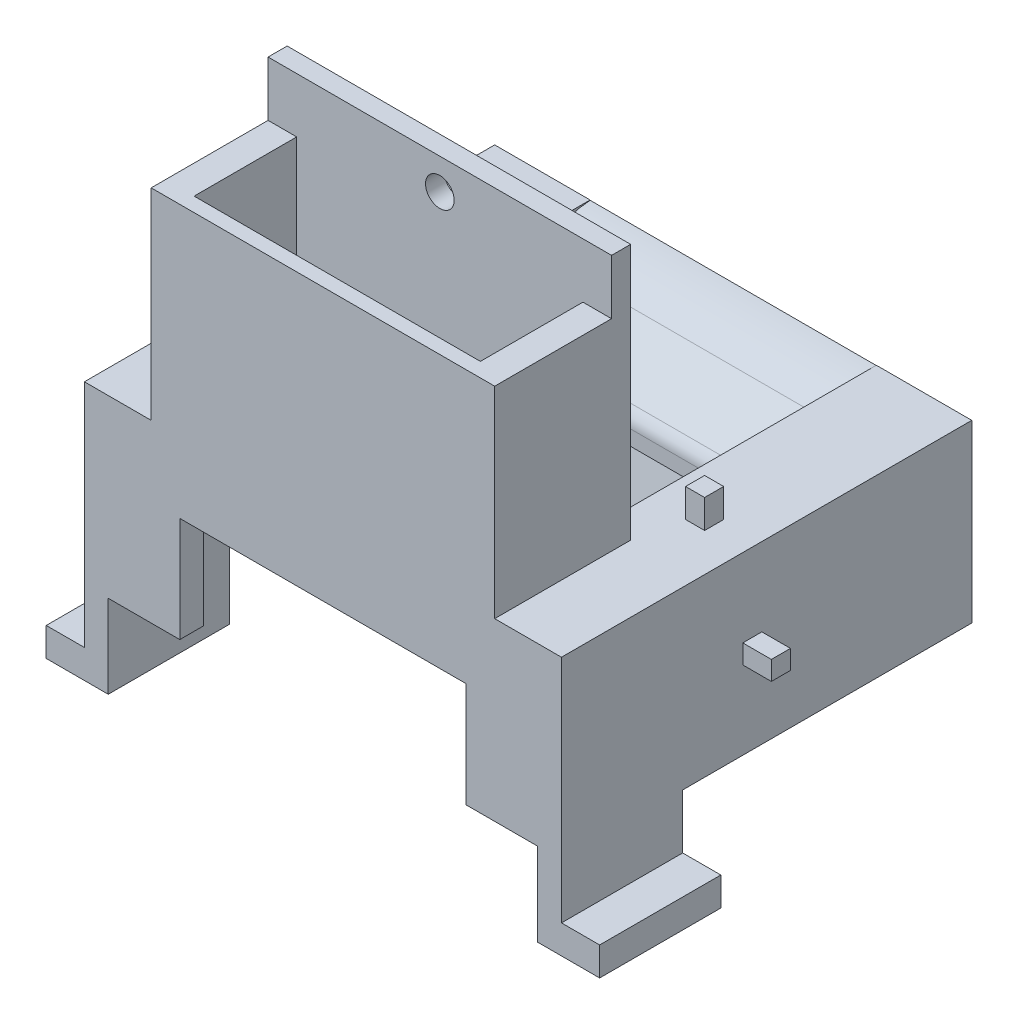
SolidWorks part; units mm, degrees
ref_plane "Front Plane" through (0, 0, 0) normal (0, 0, 1) x (1, 0, 0)
ref_plane "Top Plane" through (0, 0, 0) normal (0, 1, 0) x (1, 0, 0)
ref_plane "Right Plane" through (0, 0, 0) normal (1, 0, 0) x (0, 0, -1)
sketch "Sketch1" plane through (0, 0, 0) normal (0, 0, 1) x (1, 0, 0)
  line L1 (-25, 9.2) -> (25, 9.2)
  line L2 (-25, 9.2) -> (-25, -9.2)
  line L3 (-25, -9.2) -> (25, -9.2)
  line L4 (25, 9.2) -> (25, -9.2)
  line L5 (-25, 9.2) -> (25, -9.2) construction
  line L6 (-25, -9.2) -> (25, 9.2) construction
  point P0 (0, 0)
  dimension "D1" = 50
  dimension "D2" = 18.4
extrude "Boss-Extrude1" add sketch "Sketch1" along normal blind 43
sketch "Sketch2" plane through (0, -9.2, 0) normal (0, -1, 0) x (-1, 0, 0)
  line L0 (-25, -43) -> (-25, 0) construction
  line L1 (-22.5, -14.5) -> (-15, -14.5)
  line L2 (-22.5, -14.5) -> (-22.5, -9.5)
  line L3 (-22.5, -9.5) -> (-15, -9.5)
  line L4 (-15, -14.5) -> (-15, -9.5)
  line L5 (25, 0) -> (-25, 0) construction
  line L6 (22.5, -14.5) -> (15, -14.5)
  line L7 (22.5, -14.5) -> (22.5, -9.5)
  line L8 (22.5, -9.5) -> (15, -9.5)
  line L9 (15, -14.5) -> (15, -9.5)
  line L10 (-22.5, -12) -> (-25, -12) construction
  line L11 (15, -12.9) -> (-15, -12.9)
  line L12 (15, -12.9) -> (15, -11.1)
  line L13 (15, -11.1) -> (-15, -11.1)
  line L14 (-15, -12.9) -> (-15, -11.1)
  line L15 (22.5, -12) -> (25, -12) construction
  line L19 (25, -43) -> (25, 0) construction
  point P12 (15, -12)
  point P13 (-15, -12)
  point P15 (15, -12)
  line M14 (-25, 0) -> (-25, -43)
  line M16 (25, -43) -> (25, 0)
  dimension "D1" = 5
  dimension "D2" = 7.5
  dimension "D3" = 1.8
  dimension "D4" = 2.5
  dimension "IRdist" = 12
extrude "Cut-Extrude1" cut sketch "Sketch2" against normal blind 15.6 contours L9 L6 L8 M16 | L9 L13 L4 L11 | L1 L4 L3 M14 region at (18.75, -9.2, 12) region at (0, -9.2, 12) region at (-18.75, -9.2, 12)
sketch "Sketch3" plane through (0, 0, 0) normal (1, 0, 0) x (0, 0, -1)
  line L0 (-2.5, -9.2) -> (-2.5, 6.2)
  line L1 (-43, -9.2) -> (0, -9.2) construction
  line L2 (-2.5, 6.2) -> (-11.8253, -1.1447)
  line L3 (-11.8253, -1.1447) -> (-40.5, 6.2)
  line L4 (-40.5, 6.2) -> (-40.5, -9.2)
  line L5 (-40.5, -9.2) -> (-2.5, -9.2)
  line L6 (-43, 9.2) -> (0, 9.2) construction
  line L7 (-43, 9.2) -> (0, 9.2) construction
  line L8 (-43, 9.2) -> (-43, -9.2) construction
  line L9 (-2.7315, 9.2) -> (-12, 1.9)
  line L10 (-12, 1.9) -> (-40.5, 9.2)
  line L11 (-40.5, 9.2) -> (-2.7315, 9.2)
  line L12 (-14.5, 6.4) -> (-9.5, 6.4) construction
  line L13 (0, 9.2) -> (0, -9.2) construction
  line L14 (-21.6873, 4.3813) -> (-12, 1.6)
  line L15 (-12, 1.6) -> (-12, 1.9)
  dimension "D1" = 2.5
  dimension "D3" = 2.5
  dimension "D4" = 4.5
  dimension "D2" = 3
  dimension "D5" = 2.5
  dimension "D6" = 12
  dimension "D7" = 0.3
  dimension "D8" = 10
extrude "Cut-Extrude2" cut sketch "Sketch3" against normal up to vertex (22.5 mm away) contours L4 L5 L0 L2 L3 region at (0, -3.1445, 22.5098) up to point (-22.5, -9.2, 14.5)
mirror "Mirror3" about plane through (0, 0, 0) normal (1, 0, 0) of "Cut-Extrude2"
extrude "Cut-Extrude3" cut sketch "Sketch3<3>" against normal up to vertex (15 mm away) contours L11 L10 L9 | L14 L15 L10 region at (0, 6.7667, 18.4105) region at (0, 2.6271, 15.2291) up to point (-15, -0.8695, 12.9)
sketch "Sketch3<3>" plane through (0, 0, 0) normal (1, 0, 0) x (0, 0, -1) same geometry as "Sketch3"
mirror "Mirror4" about plane through (0, 0, 0) normal (1, 0, 0) of "Cut-Extrude3"
sketch "Sketch12" plane through (22.5, 0, 0) normal (-1, 0, 0) x (0, 0, 1)
  line L0 (9.5, 6.4) -> (9.5, 0.6867)
  line L1 (9.5, 0.6867) -> (9.625, 6.4)
  line L3 (9.625, 6.4) -> (9.5, 6.4)
  line L4 (14.5, 6.4) -> (14.5, 0.6867)
  line L5 (14.5, 0.6867) -> (14.375, 6.4)
  line L6 (14.375, 6.4) -> (14.5, 6.4)
  dimension "D1" = 4.75
extrude "Boss-Extrude3" add sketch "Sketch12" along normal up to surface (7.5 mm away) up to face at (15, 5.9669, 16.1312)
extrude "Boss-Extrude4" add sketch "Sketch12<2>" against normal up to surface (-37.5 mm away) from surface up to face at (-15, 1.6478, 10.3) starting at face at (-22.5, 0.8784, 16.75)
sketch "Sketch12<2>" plane through (22.5, 0, 0) normal (-1, 0, 0) x (0, 0, 1) same geometry as "Sketch12"
sketch "Sketch17" plane through (-15, 0, 0) normal (1, 0, 0) x (0, 0, -1)
  line L0 (-43, 9.2) -> (-43, 10.7)
  line L1 (-43, 10.7) -> (-21.6873, 4.3813)
  line L2 (-21.6873, 4.3813) -> (-40.5, 9.2)
  line L3 (-40.5, 9.2) -> (-43, 9.2)
  dimension "D1" = 1.5
extrude "Boss-Extrude7" add sketch "Sketch17" along normal up to surface (30 mm away) up to face at (15, 5.9577, 16.136)
sketch "Sketch18" plane through (15, 0, 0) normal (1, 0, 0) x (0, 0, -1)
  line L0 (-43, 10.7) -> (-43, 9.2)
  line L1 (-43, 9.2) -> (-37.9406, 9.2)
  line L2 (-43, 9.2) -> (-37.9406, 9.2) construction
  line L4 (-37.9406, 9.2) -> (-43, 10.7)
  line L5 (-43, 10.7) -> (-37.9406, 9.2) construction
extrude "Mtrl Rmv" cut sketch "Sketch18" against normal through all
ref_plane "Plane4" through (0, 0, 30.75) normal (0, 0, 1) x (1, 0, 0)
sketch "Sketch23" plane through (15, 0, 0) normal (-1, 0, 0) x (0, 0, 1)
  line L0 (21.6873, 4.3813) -> (14.4645, 2.3076) construction
  line L1 (30.75, -26.9374) -> (30.75, 26.9374) construction
  point P0 (30.75, 6.9833)
sketch "Sketch22" plane through (0, 0, 30.75) normal (0, 0, 1) x (1, 0, 0)
  line L0 (18, 36.05) -> (18, 11.9833)
  line L1 (18, 11.9833) -> (18, 9.2)
  line L2 (18, 36.05) -> (-18, 36.05)
  line L3 (18, 11.9833) -> (-18, 11.9833)
  line L4 (-18, 11.9833) -> (-18, 36.05)
  line L5 (15, 11.9833) -> (15, 6.9833) construction
  line L6 (15, 6.4) -> (15, 2.3076) construction
  line L7 (25, 9.2) -> (-25, 9.2) construction
  line L8 (15, 11.9833) -> (15, 9.2)
  line L9 (0, 11.9833) -> (0, 0) construction
  line L10 (18, 9.2) -> (15, 9.2)
  line L11 (-25, -9.2) -> (25, -9.2) construction
  line L12 (-18, 11.9833) -> (-18, 9.2)
  line L13 (-18, 9.2) -> (-15, 9.2)
  line L14 (-15, 9.2) -> (-15, 11.9833)
  dimension "D1" = 5
  dimension "D2" = 3
  dimension "D3" = 45.25
extrude "Boss-Extrude8" add sketch "Sketch22" against normal blind 2 contours L4 L3 L0 L2 | L10 L1 L3 L8 | L13 L14 L3 L12 region at (0, 24.0166, 30.75) region at (16.5, 10.5916, 30.75) region at (-16.5, 10.5916, 30.75)
sketch "Sketch25" plane through (18, 0, 0) normal (1, 0, 0) x (0, 0, -1)
  line L0 (-43, -9.2) -> (0, -9.2) construction
  line L1 (-43, 9.2) -> (-41.5, 9.2)
  line L2 (-43, 9.2) -> (-43, 30.3)
  line L3 (-43, 30.3) -> (-41.5, 30.3)
  line L4 (-41.5, 9.2) -> (-41.5, 30.3)
  line L5 (-35.7642, 18.6552) -> (-41.5, 23.3)
  line L6 (-35.7642, 18.6552) -> (-41.5, 18.6552)
  line L7 (-30.75, 18.6552) -> (-34.324, 11.9833)
  line L8 (-30.75, 36.05) -> (-30.75, 9.2) construction
  line L10 (-41.5, 10.2553) -> (-37.9406, 9.2)
  line L11 (-43, 9.2) -> (0, 9.2) construction
  line L12 (-21.6873, 4.3813) -> (-37.9406, 9.2) construction
  line L13 (-37.9406, 9.2) -> (-41.5, 9.2)
  line L14 (-34.324, 11.8778) -> (-37.9406, 9.2) construction
  line L15 (-35.7642, 18.6552) -> (-32.267, 15.8233) construction
  line L16 (-34.324, 11.8778) -> (-34.324, 8.1278) construction
  line L18 (-30.75, 11.9833) -> (-30.75, 6.9833) construction
  line L19 (-30.75, 36.05) -> (-30.75, 9.2) construction
  line L20 (-30.75, 11.9833) -> (-34.324, 11.9833)
  line L21 (-34.324, 11.8778) -> (-34.324, 11.9833) construction
  line L22 (-21.6873, 4.3813) -> (-14.4645, 2.3076) construction
  line M36 (-30.75, 36.05) -> (-30.75, 9.2)
  dimension "D1" = 1.5
  dimension "D2" = 39.5
  dimension "D3" = 3.75
  dimension "D4" = 51
  dimension "D5" = 7
  dimension "D6" = 4.5
  dimension "D7" = 4.5
  dimension "D8" = 5
extrude "Boss-Extrude9" add sketch "Sketch25" against normal up to surface (36 mm away) contours L1 L4 L3 L2 | L6 L5 L4 | L13 L10 L4 | M36 | L7 M36 region at (18, 19.75, 42.25) region at (18, 9.5518, 40.3135) region at (18, 20.2035, 39.5881) region at (18, 14.2073, 31.9413) up to face at (-18, 22.625, 29.75)
sketch "Sketch27" plane through (0, 0, 43) normal (0, 0, 1) x (1, 0, 0)
  line L0 (-18, 30.3) -> (18, 30.3) construction
  line L1 (-18, 9.2) -> (-15, 9.2)
  line L2 (-18, 9.2) -> (-18, 30.3)
  line L3 (-18, 30.3) -> (-15, 30.3)
  line L4 (-15, 9.2) -> (-15, 30.3)
  line L5 (25, 9.2) -> (18, 9.2) construction
  line L6 (18, 9.2) -> (15, 9.2)
  line L7 (18, 9.2) -> (18, 30.3)
  line L8 (18, 30.3) -> (15, 30.3)
  line L9 (15, 9.2) -> (15, 30.3)
extrude "Boss-Extrude10" add sketch "Sketch27" against normal up to surface (14.25 mm away) up to face at (0, 16.6083, 28.75)
sketch "Sketch28" plane through (0, 0, 28.75) normal (0, 0, -1) x (-1, 0, 0)
  line L0 (18, 30.3) -> (-18, 30.3) construction
  line L1 (-18, 36.05) -> (18, 36.05) construction
  circle A0 centre (0, 32.8) radius 1.5
  point P7 (0, 36.05)
  dimension "D1" = 3
  dimension "D2" = 2.5
extrude "Cut-Extrude4" cut sketch "Sketch28" against normal through all
sketch "Sketch4" plane through (0, 0, 43) normal (0, 0, 1) x (1, 0, 0)
  line L0 (-25, -9.2) -> (25, -9.2) construction
  line L1 (-15, -9.2) -> (15, -9.2)
  line L2 (-15, -9.2) -> (-15, 1.8)
  line L3 (-15, 1.8) -> (15, 1.8)
  line L4 (15, -9.2) -> (15, 1.8)
  point P6 (0, 1.8)
  dimension "D1" = 30
  dimension "D2" = 11
extrude "Wire Hole" cut sketch "Sketch4" against normal up to surface (2.5 mm away) up to face at (0, -1.5, 40.5)
sketch "Sketch13" plane through (0, 0, 0) normal (0, 0, -1) x (-1, 0, 0)
  line L0 (-13, 0) -> (13, 0) construction
  line L1 (-15, 1) -> (-13, 1)
  line L2 (-15, 1) -> (-15, -1)
  line L3 (-15, -1) -> (-13, -1)
  line L4 (-13, 1) -> (-13, -1)
  line L5 (13, 1) -> (15, 1)
  line L6 (13, 1) -> (13, -1)
  line L7 (13, -1) -> (15, -1)
  line L8 (15, 1) -> (15, -1)
  point P16 (0, 0)
  dimension "D1" = 2
  dimension "D2" = 7.5
extrude "Front Shield Pegs" add sketch "Sketch13" along normal blind 2.9972
sketch "Sketch14" plane through (0, 9.2, 0) normal (0, 1, 0) x (1, 0, 0)
  line L0 (19, -23) -> (-19, -23) construction
  line L1 (21, -22) -> (19, -22)
  line L2 (21, -22) -> (21, -24)
  line L3 (21, -24) -> (19, -24)
  line L4 (19, -22) -> (19, -24)
  line L5 (-19, -22) -> (-21, -22)
  line L6 (-19, -22) -> (-19, -24)
  line L7 (-19, -24) -> (-21, -24)
  line L8 (-21, -22) -> (-21, -24)
  line L10 (25, -43) -> (18, -43) construction
  point P8 (0, -23)
  point P12 (21, -23)
  dimension "D1" = 2
  dimension "D2" = 20
  dimension "D3" = 4
extrude "Top Shield Pegs" add sketch "Sketch14" along normal blind 2.9972
fillet "Fillet9" radius 10 1 edges at (0, 9.2, 2.7315)
fillet "Fillet10" radius 2 1 edges at (0, 2.6089, 11.1)
ref_plane "Plane3" through (0, 0, 19) normal (0, 0, 1) x (1, 0, 0)
sketch "Sketch19" plane through (0, 0, 19) normal (0, 0, 1) x (1, 0, 0)
  line L0 (22.5, -9.2) -> (22.5, -17.915)
  line L1 (22.5, -17.915) -> (29, -17.915)
  line L2 (29, -17.915) -> (29, -14.915)
  line L3 (29, -14.915) -> (25, -14.915)
  line L4 (25, -14.915) -> (25, -9.2)
  line L5 (25, -9.2) -> (22.5, -9.2)
  line L6 (-22.5, -9.2) -> (-22.5, -17.915)
  line L7 (-22.5, -17.915) -> (-29, -17.915)
  line L8 (-29, -17.915) -> (-29, -14.915)
  line L9 (-29, -14.915) -> (-25, -14.915)
  line L10 (-25, -14.915) -> (-25, -9.2)
  line L11 (-25, -9.2) -> (-22.5, -9.2)
  dimension "D1" = 4
  dimension "D2" = 5.715
  dimension "D3" = 3
extrude "Legs" add sketch "Sketch19" against normal blind 12.7 from surface starting at face at (0, 5.35, 43)
sketch "Sketch29" plane through (-25, 0, 0) normal (-1, 0, 0) x (0, 0, 1)
  line L0 (23, 1) -> (23, 12.1972) construction
  line L1 (22, 1) -> (24, 1)
  line L2 (22, 1) -> (22, -1)
  line L3 (22, -1) -> (24, -1)
  line L4 (24, 1) -> (24, -1)
  line L5 (22, 12.1972) -> (24, 12.1972) construction
  line L7 (22, 12.1972) -> (22, 9.2) construction
  line L8 (22, 0) -> (-2.9972, 0) construction
  line L9 (-2.9972, -1) -> (-2.9972, 1) construction
extrude "Side Shield Pegs1" add sketch "Sketch29" along normal blind 2.9972
extrude "Side Shield Pegs2" add sketch "Sketch29<2>" against normal blind 2.9972 from surface starting at face at (25, -4.9717, 24.4333)
sketch "Sketch29<2>" plane through (-25, 0, 0) normal (-1, 0, 0) x (0, 0, 1) same geometry as "Sketch29"
fillet "Fillet3" [suppressed] radius 3
fillet "Fillet5" [suppressed] radius 3
fillet "Fillet6" [suppressed] radius 3 tangent propagation no
sketch "Sketch5" [suppressed] plane through (0, 0, 0) normal (1, 0, 0) x (0, 0, -1)
  line L0 (-40, 3.5229) -> (-61, 15.1419)
  line L1 (-45.2, 16.8) -> (-45.2, 18.347)
  line L2 (-61, 15.1419) -> (-61, 22.3)
  line L3 (-61, 22.3) -> (-45.2, 22.3)
  line L5 (-45.2, 16.8) -> (-40, 13.9229)
  line L6 (-40, 13.9229) -> (-40, 3.5229)
  line L7 (-40, 6.2) -> (-40, -9.2) construction
  line L8 (-45.2, 18.347) -> (-45.2, 22.3)
  line L10 (0, 9.2) -> (-40, 9.2) construction
  line L11 (-45.2, 22.3) -> (-61, 22.3)
  line L12 (-45.2, 22.3) -> (-45.2, 30.675)
  line L13 (-45.2, 30.675) -> (-61, 30.675)
  line L14 (-61, 22.3) -> (-61, 30.675)
  line L19 (-40, 13.9229) -> (-35.4398, 11.3998)
  line L20 (-35.4398, 11.3998) -> (-35.4398, 9.2)
  line L22 (-35.4398, 9.2) -> (-40, 9.2)
  dimension "D1" = 24
  dimension "D2" = 21
  dimension "D3" = 13.1
  dimension "D4" = 5.2
  dimension "D5" = 5.5
  dimension "D6" = 10.4
  dimension "D7" = 8.375
extrude "Ramp Extrude" [suppressed] add sketch "Sketch5" along normal mid plane 15
ref_plane "Plane2" [suppressed] through (0, 7.2819, -2.3953) normal (0, 0.9499, -0.3125) x (1, 0, 0)
sketch "Sketch7" [suppressed] plane through (0, 0, 0) normal (1, 0, 0) x (0, 0, -1)
  line L1 (-61, 15.1419) -> (-61, 30.675) construction
  line L2 (-60, 19.3) -> (-60, 22.3)
  line L3 (-60, 22.3) -> (-45.2, 22.3)
  line L4 (-60, 22.3) -> (-45.2, 22.3)
  line L5 (-45.2, 22.3) -> (-45.2, 16.8)
  line L8 (-60, 22.3) -> (-60, 30.675)
  line L9 (-35.4398, 11.3998) -> (-35.4398, 9.2)
  line L10 (-45.2, 27.675) -> (-60, 27.675) construction
  line L11 (-60, 30.675) -> (-45.2, 30.675)
  line L12 (-45.2, 22.3) -> (-45.2, 30.675)
  line L13 (-45.2, 30.675) -> (-61, 30.675) construction
  line L14 (-45.2, 16.8) -> (-45.2, 30.675) construction
  line L17 (-45.2, 16.8) -> (-35.4398, 11.3998)
  line L21 (-35.4398, 9.2) -> (-54.0763, 18.2247)
  arc A0 (-60, 27.675) -> (-54.0763, 18.2247) centre (-49.5, 27.675) ccw
  dimension "D5" = 10.5
  dimension "D1" = 1
  dimension "D2" = 3
  dimension "D3" = 5.5
  dimension "D4" = 3
extrude "Ramp Shell Cut" [suppressed] cut sketch "Sketch7" against normal mid plane 13
sketch "Sketch8" [suppressed] plane through (-7.5, 0, 0) normal (-1, 0, 0) x (0, 0, 1)
  line L0 (45.2, 23.7375) -> (49.15, 30.675)
  line L1 (45.2, 16.8) -> (45.2, 30.675) construction
  line L2 (45.2, 30.675) -> (61, 30.675) construction
  line L3 (49.15, 30.675) -> (45.2, 30.675)
  line L4 (45.2, 30.675) -> (45.2, 23.7375)
  line L5 (45.2, 23.7375) -> (53.1, 23.7375) construction
  point P9 (53.1, 30.675)
  point P12 (49.15, 23.7375)
extrude "Ramp Corner Cuts" [suppressed] cut sketch "Sketch8" against normal through all
equation "\"bottomThickness\"= .220in"
equation "\"wallThickness\"= .118in"
equation "\"D1@Front Shield Pegs\" = \"wallThickness\""
equation "\"D1@Top Shield Pegs\" = \"wallThickness\""
equation "\"IRdist\"=12"
equation "\"IRdist@Sketch2\"=\"IRdist\""
equation "\"D6@Sketch3\"=\"IRdist\""
equation "\"D1@Side Shield Pegs1\" = \"wallThickness\""
equation "\"D1@Side Shield Pegs2\" = \"wallThickness\""
equation "\"D2@Sketch19\"=\"bottomThickness\"+.005in"
